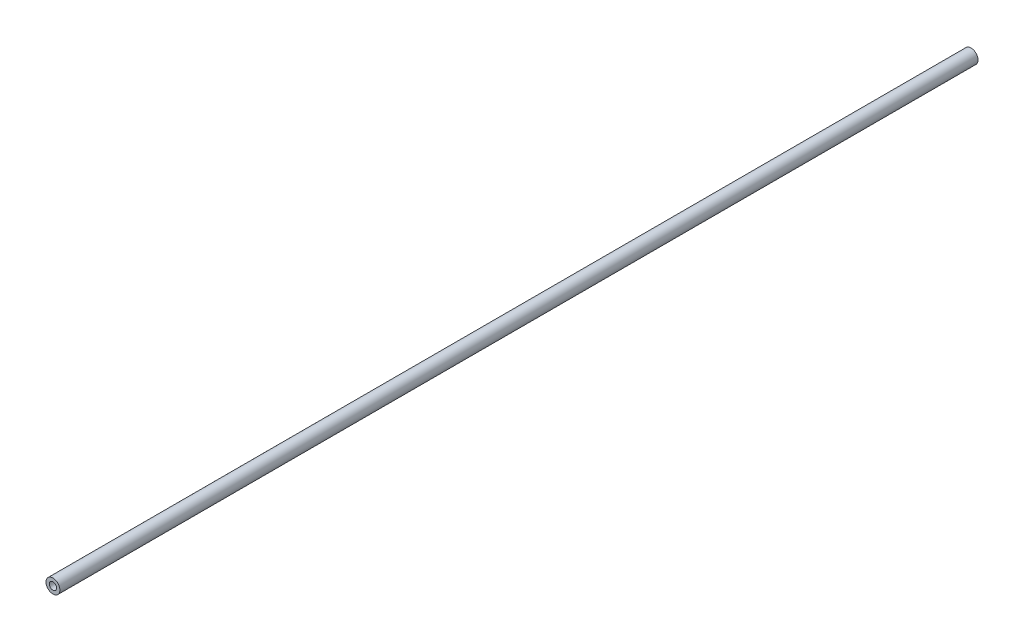
SolidWorks part; units mm, degrees
material "6061-T6 (SS)"
ref_plane "Front Plane" through (0, 0, 0) normal (0, 0, 1) x (1, 0, 0)
ref_plane "Top Plane" through (0, 0, 0) normal (0, 1, 0) x (1, 0, 0)
ref_plane "Right Plane" through (0, 0, 0) normal (1, 0, 0) x (0, 0, -1)
sketch "Sketch1" plane through (0, 0, 0) normal (0, 0, 1) x (1, 0, 0)
  circle A0 centre (0, 0) radius 4.7625
  circle A1 centre (0, 0) radius 2.4892
  dimension "D1" = 4.9784
  dimension "D2" = 9.525
extrude "Boss-Extrude1" add sketch "Sketch1" along normal blind 628.65
